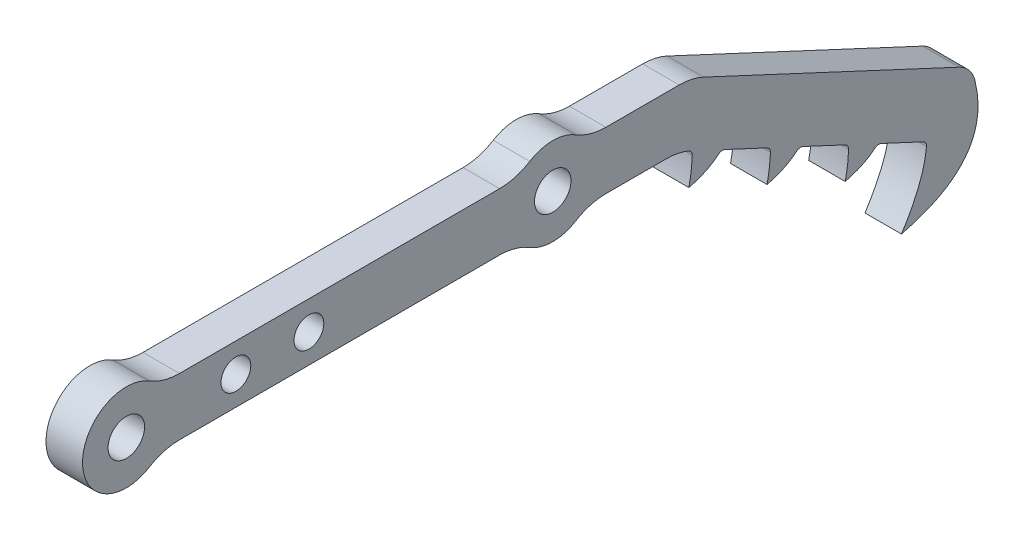
SolidWorks part; units mm, degrees
material "6061 Alloy"
ref_plane "Front Plane" through (0, 0, 0) normal (0, 0, 1) x (1, 0, 0)
ref_plane "Top Plane" through (0, 0, 0) normal (0, 1, 0) x (1, 0, 0)
ref_plane "Right Plane" through (0, 0, 0) normal (1, 0, 0) x (0, 0, -1)
sketch "Sketch1" plane through (0, 0, 0) normal (1, 0, 0) x (0, 0, -1)
  line L0 (-57.9219, 44.5435) -> (-40.0493, 54.8622)
  line L1 (-40.0493, 49.8622) -> (56.1047, 49.8622)
  line L2 (56.1047, 49.8622) -> (102.5472, 28.2057)
  line L3 (-40.0493, 59.8622) -> (58.3217, 59.8622)
  line L4 (58.3217, 59.8622) -> (106.7734, 37.2688)
  line L5 (56.1047, 49.8622) -> (84.5622, 36.5923) construction
  line L6 (58.3217, 59.8622) -> (88.7883, 45.6554) construction
  line L7 (102.5472, 28.2057) -> (106.7734, 37.2688)
  line L8 (102.5472, 28.2057) -> (111.6103, 23.9795)
  line L9 (93.4842, 32.4319) -> (106.7734, 37.2688)
  line L10 (56.1047, 49.8622) -> (58.3217, 59.8622) construction
  circle A0 centre (-57.9219, 44.5435) radius 15.875
  circle A1 centre (-40.0493, 54.8622) radius 4.7625
  circle A2 centre (-40.0493, 54.8622) radius 2.5
  circle A3 centre (-40.0493, 54.8622) radius 5
  circle A4 centre (-40.0493, 54.8622) radius 7.62
  circle A6 centre (34.1047, 54.8622) radius 7.62
  parabola Q0 (106.7734, 37.2688) -> (94.7552, 18.0752) focus (102.5472, 28.2057) apex (107.0788, 26.0926)
  parabola Q1 (99.1632, 29.7837) -> (94.7552, 18.0752) focus (93.4842, 32.4319) apex (98.5101, 34.2612)
  parabola Q2 (93.4202, 43.4955) -> (84.9631, 30.8885) focus (87.9414, 37.2725) apex (91.341, 34.5621)
  parabola Q3 (85.5686, 36.123) -> (84.9631, 30.8885) focus (78.3442, 40.2408) apex (83.762, 43.3694)
  parabola Q4 (79.8256, 49.8348) -> (71.3685, 37.2277) focus (74.3468, 43.6117) apex (77.7464, 40.9013)
  parabola Q5 (71.974, 42.4623) -> (71.3685, 37.2277) focus (64.7496, 46.58) apex (70.1674, 49.7086)
  parabola Q6 (66.2309, 56.1741) -> (57.7739, 43.567) focus (60.7522, 49.951) apex (64.1518, 47.2406)
  parabola Q7 (58.3794, 48.8015) -> (57.7739, 43.567) focus (51.155, 52.9193) apex (56.5728, 56.0479)
  point P12 (93.4842, 32.4319)
  point P19 (100.1288, 34.8504)
  point P46 (57.2132, 54.8622)
  point P47 (34.1047, 54.8622)
  dimension "D1" = 10
  dimension "D5" = 10
  dimension "D2" = 12.4745
  dimension "D3" = 5
  dimension "D4" = 15
  dimension "D6" = 5
  dimension "D7" = 22
extrude "Boss-Extrude1" add sketch "Sketch1" along normal blind 6.35 contours A0 A4 L0 A3 | L0 A4 A0 A3 | A0 A4 L1 A3 | L3 A4 A0 A3 | L0 A3 A0 | A0 A3 L0 | A3 A0 A1 | A2 A1 | A2 | L1 A4 L3 A3 | A6 L3 A4 L1 | L3 A6 L1 | L3 A6 | L1 A6 | Q6 L4 L3 A6 L1 L2 | L2 Q7 Q6 | L4 Q6 L2 Q4 | L2 Q5 Q4 | L4 Q4 L2 Q2 | L2 Q3 Q2 | L4 Q2 L2 L9 | L9 L2 L7 | Q0 L7 L8 | L2 Q1 Q0 L8 | A6 region at (0, 53.5286, 46.341) region at (0, 50.0803, 44.3502) region at (0, 52.862, 44.5166) region at (0, 51.9936, 44.0152) region at (0, 59.6292, 42.1434) region at (0, 48.8401, 39.3562) region at (0, 57.2087, 40.6781) region at (0, 53.0598, 44.5079) region at (0, 59.3323, 41.2471) region at (0, 54.8622, 34.7231) region at (0, 54.8622, 2.9723) region at (0, 60.9274, -34.1047) region at (0, 54.8622, -34.1047) region at (0, 48.7971, -34.1047) region at (0, 54.2453, -53.6216) region at (0, 47.8087, -72.3396) region at (0, 46.1053, -60.0268) region at (0, 41.4694, -85.9342) region at (0, 37.45, -97.3772) region at (0, 39.7661, -73.6214) region at (0, 30.7591, -105.9447) region at (0, 32.6355, -100.9349) region at (0, 33.4268, -87.216) region at (0, 23.9786, -100.9688)
sketch "Sketch7" plane through (6.35, 0, 0) normal (1, 0, 0) x (0, 0, -1)
  point P0 (-40.0493, 54.8622)
  point P1 (34.1047, 54.8622)
hole_wizard "1/4 (0.2500) Dowel Hole4" positions "Sketch7" profile "Sketch8" hole size "1/4" standard "ANSI Inch" end condition through all
sketch "Sketch8" plane through (6.35, 54.8622, 40.0493) normal (0, 1, 0) x (0, 0, -1)
  line L0 (0, 0) -> (0, 6.35)
  line L1 (0, 6.35) -> (3.175, 6.35)
  line L2 (3.175, 6.35) -> (3.175, 0)
  line L5 (3.175, 0) -> (0, 0)
  line L11 (0, -6.35) -> (0, 107.95) construction
  dimension "Thru Hole Dia." = 6.35
  dimension "Thru Hole Depth" = 6.35
fillet "Fillet1" radius 10 2 edges at (3.175, 59.8622, 34.2992) (3.175, 49.8622, 34.2992)
fillet "Fillet2" radius 10 2 edges at (3.175, 49.8622, -56.1047) (3.175, 59.8622, -58.3217)
fillet "Fillet4" radius 5 1 edges at (3.175, 37.2688, -106.7734)
fillet "Fillet5" radius 1 7 edges at (3.175, 33.7664, -90.6224) (3.175, 40.1057, -77.0278) (3.175, 46.4449, -63.4331) (3.175, 48.8015, -58.3794) (3.175, 42.4623, -71.974) (3.175, 36.123, -85.5686) (3.175, 29.7837, -99.1632)
fillet "Fillet6" radius 10 4 edges at (3.175, 49.8622, -28.3545) (3.175, 49.8622, -39.8549) (3.175, 59.8622, -28.3545) (3.175, 59.8622, -39.8549)
sketch "Sketch9" plane through (6.35, 0, 0) normal (1, 0, 0) x (0, 0, -1)
  circle A0 centre (-40.0493, 54.8622) radius 3.175 construction
  point P1 (-8.2993, 54.8622)
  point P3 (-20.9993, 54.8622)
  point P4 (0, 0)
  dimension "D1" = 12.7
  dimension "D2" = 19.05
hole_wizard "#6 (0.204) Diameter Hole1" positions "Sketch9" profile "Sketch10" hole size "#6" standard "ANSI Inch" end condition through all
sketch "Sketch10" plane through (6.35, 54.8622, 20.9993) normal (0, 1, 0) x (0, 0, -1)
  line L0 (0, 0) -> (0, 6.35)
  line L1 (0, 6.35) -> (2.5908, 6.35)
  line L2 (2.5908, 6.35) -> (2.5908, 0)
  line L5 (2.5908, 0) -> (0, 0)
  line L11 (0, -6.35) -> (0, 107.95) construction
  dimension "Thru Hole Dia." = 5.1816
  dimension "Thru Hole Depth" = 6.35
